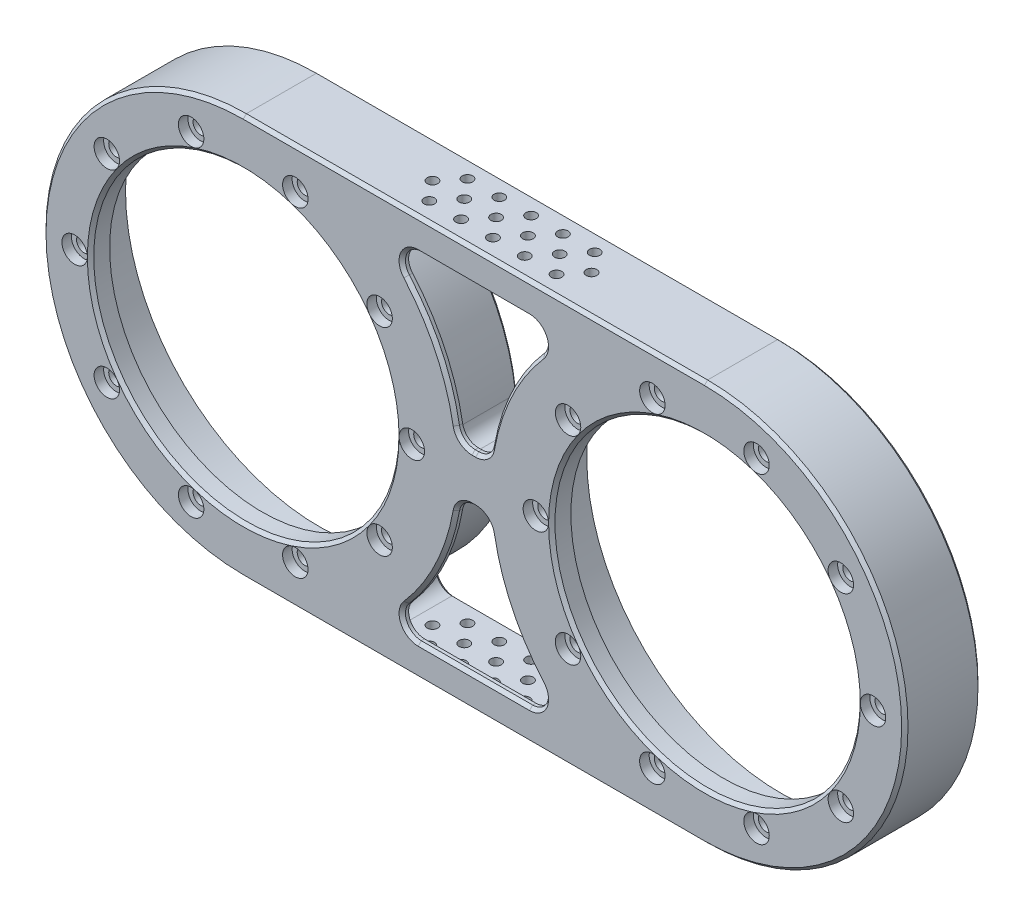
SolidWorks part; units mm, degrees
material "7075-T6 (SN)"
ref_plane "前视基准面" through (0, 0, 0) normal (0, 0, 1) x (1, 0, 0)
ref_plane "上视基准面" through (0, 0, 0) normal (0, 1, 0) x (1, 0, 0)
ref_plane "右视基准面" through (0, 0, 0) normal (1, 0, 0) x (0, 0, -1)
sketch "草图1" plane through (0, 0, 0) normal (0, 0, 1) x (1, 0, 0)
  line L0 (0, 63) -> (145, 63)
  line L1 (0, -63) -> (145, -63)
  arc A0 (0, 63) -> (0, -63) centre (0, 0) ccw
  arc A1 (145, -63) -> (145, 63) centre (145, 0) ccw
  circle A2 centre (0, 0) radius 60
  circle A3 centre (145, 0) radius 60
extrude "凸台-拉伸1" add sketch "草图1" against normal blind 3
sketch "草图2" plane through (0, 0, 0) normal (0, 0, 1) x (1, 0, 0)
  line L2 (0, -63) -> (145, -63)
  line L3 (145, 63) -> (0, 63)
  line L4 (0, -63) -> (145, -63)
  line L5 (145, 63) -> (0, 63)
  circle A0 centre (0, 0) radius 53 construction
  circle A1 centre (145, 0) radius 53 construction
  circle A2 centre (0, 0) radius 48
  circle A3 centre (145, 0) radius 48
  arc A6 (0, 63) -> (0, -63) centre (0, 0) ccw
  arc A7 (145, -63) -> (145, 63) centre (145, 0) ccw
  arc A8 (0, 63) -> (0, -63) centre (0, 0) ccw
  arc A9 (145, -63) -> (145, 63) centre (145, 0) ccw
  dimension "D1" = 5
  dimension "D2" = 5
  dimension "D3" = 0
extrude "凸台-拉伸2" add sketch "草图2" along normal blind 6
sketch "草图3" plane through (0, 0, -3) normal (0, 0, -1) x (-1, 0, 0)
  line L2 (0, 63) -> (-145, 63)
  line L3 (-145, -63) -> (0, -63)
  line L4 (0, 63) -> (-145, 63)
  line L5 (-145, -63) -> (0, -63)
  circle A0 centre (-145, 0) radius 61
  circle A1 centre (0, 0) radius 61
  arc A4 (0, -63) -> (0, 63) centre (0, 0) ccw
  arc A5 (-145, 63) -> (-145, -63) centre (-145, 0) ccw
  arc A6 (0, -63) -> (0, 63) centre (0, 0) ccw
  arc A7 (-145, 63) -> (-145, -63) centre (-145, 0) ccw
  dimension "D1" = 0
extrude "凸台-拉伸3" add sketch "草图3" along normal blind 15
sketch "草图4" plane through (0, 0, -18) normal (0, 0, -1) x (-1, 0, 0)
  line L0 (-84, 0) -> (-61, 0) construction
  line L1 (0, 58) -> (-145, 58)
  line L2 (0, 63) -> (-145, 63)
  line L3 (-145, -63) -> (0, -63)
  line L4 (0, 63) -> (-145, 63)
  line L5 (-145, -63) -> (0, -63)
  line L6 (-145, -58) -> (0, -58)
  line L7 (-84, -2.5) -> (-61, -2.5)
  line L8 (-84, 2.5) -> (-61, 2.5)
  circle A0 centre (0, 0) radius 61 construction
  circle A1 centre (-145, 0) radius 61 construction
  circle A2 centre (0, 0) radius 61
  circle A3 centre (-145, 0) radius 61
  circle A5 centre (-145, 0) radius 63
  arc A6 (0, -63) -> (0, 63) centre (0, 0) ccw
  arc A7 (-145, 63) -> (-145, -63) centre (-145, 0) ccw
  arc A8 (0, -63) -> (0, 63) centre (0, 0) ccw
  arc A9 (-145, 63) -> (-145, -63) centre (-145, 0) ccw
  circle A10 centre (0, 0) radius 63
  dimension "D2" = 5
  dimension "D1" = 0
  dimension "D3" = 5
  dimension "D4" = 2.5
  dimension "D5" = 2.5
extrude "切除-拉伸1" cut sketch "草图4" against normal blind 22
sketch "草图7" plane through (0, 0, 4) normal (0, 0, -1) x (-1, 0, 0)
  line L6 (-42.6028, 53) -> (-102.3972, 53)
  line L7 (-77.4149, 7.5) -> (-67.5851, 7.5)
  line L8 (-42.6028, 53) -> (-102.3972, 53)
  line L9 (-77.4149, 7.5) -> (-67.5851, 7.5)
  line L12 (-67.5851, -7.5) -> (-77.4149, -7.5)
  line L13 (-102.3972, -53) -> (-42.6028, -53)
  line L14 (-67.5851, -7.5) -> (-77.4149, -7.5)
  line L15 (-102.3972, -53) -> (-42.6028, -53)
  arc A6 (-42.6028, 53) -> (-67.5851, 7.5) centre (0, 0) ccw
  arc A7 (-77.4149, 7.5) -> (-102.3972, 53) centre (-145, 0) ccw
  arc A8 (-42.6028, 53) -> (-67.5851, 7.5) centre (0, 0) ccw
  arc A9 (-77.4149, 7.5) -> (-102.3972, 53) centre (-145, 0) ccw
  arc A12 (-67.5851, -7.5) -> (-42.6028, -53) centre (0, 0) ccw
  arc A13 (-102.3972, -53) -> (-77.4149, -7.5) centre (-145, 0) ccw
  arc A14 (-67.5851, -7.5) -> (-42.6028, -53) centre (0, 0) ccw
  arc A15 (-102.3972, -53) -> (-77.4149, -7.5) centre (-145, 0) ccw
  dimension "D1" = 5
  dimension "D2" = 5
extrude "切除-拉伸2" cut sketch "草图7" against normal blind 20
fillet "圆角2" radius 5 16 edges at (67.5851, 7.5, 5) (77.4149, 7.5, 5) (42.6028, -53, 5) (102.3972, -53, 5) (77.4149, -7.5, 5) (67.5851, -7.5, 5) (42.6028, 53, 5) (102.3972, 53, 5) (82.0496, 2.5, -7) (62.9504, 2.5, -7) (24.5967, 58, -7) (82.0496, -2.5, -7) (120.4033, -58, -7) (24.5967, -58, -7) (62.9504, -2.5, -7) (120.4033, 58, -7)
chamfer "倒角2" distance 1 angle 45 44 edges at (193, 0, 6) (72.5, 63, 6) (208, 0, 6) (72.5, -63, 6) (-63, 0, 6) (48, 0, 6) (68.7032, 8.6737, 6) (72.5, 7.5, 6) (76.2968, 8.6737, 6) (83.6169, 29.2595, 6) (94.5518, 50.069, 6) (72.5, 53, 6) (50.4482, 50.069, 6) (61.3831, 29.2595, 6) (50.4482, -50.069, 6) (72.5, -53, 6) (94.5518, -50.069, 6) (83.6169, -29.2595, 6) (76.2968, -8.6737, 6) (72.5, -7.5, 6) (68.7032, -8.6737, 6) (61.3831, -29.2595, 6) (60, 0, -3) (205, 0, -3) (89.7765, -30.3211, -18) (80.7497, -3.7746, -18) (107.1134, -54.6605, -18) (72.5, -2.5, -18) (72.5, -58, -18) (64.2503, -3.7746, -18) (37.8866, -54.6605, -18) (55.2235, -30.3211, -18) (72.5, -63, -18) (-63, 0, -18) (208, 0, -18) (72.5, 63, -18) (72.5, 2.5, -18) (64.2503, 3.7746, -18) (80.7497, 3.7746, -18) (55.2235, 30.3211, -18) (89.7765, 30.3211, -18) (37.8866, 54.6605, -18) (107.1134, 54.6605, -18) (72.5, 58, -18)
sketch "草图8" plane through (0, 0, 6) normal (0, 0, 1) x (1, 0, 0)
  circle A0 centre (145, 0) radius 53 construction
  circle A1 centre (0, 0) radius 53 construction
  point P6 (198, 0)
  point P7 (53, 0)
hole_wizard "打孔尺寸(%根据)内六角圆柱头螺钉的类型1" positions "草图9" profile "草图10" counterbore size "M4" standard "GB"
sketch "草图9" plane through (0, 0, 6) normal (0, 0, 1) x (1, 0, 0)
  point P0 (198, 0)
sketch "草图10" plane through (198, 0, 6) normal (1, 0, 0) x (0, -1, 0)
  line L0 (0, 0) -> (0, 11.5421)
  line L1 (0, 11.5421) -> (2.4, 10.1)
  line L2 (2.4, 10.1) -> (2.4, 3)
  line L3 (2.4, 3) -> (4, 3)
  line L4 (4, 3) -> (4, 0)
  line L5 (4, 0) -> (0, 0)
  line L10 (0, 11.5421) -> (-2.4, 10.1) construction
  line L11 (0, -6.35) -> (0, 107.95) construction
  dimension "孔直径" = 4.8
  dimension "孔深度" = 10.1
  dimension "柱形沉头孔直径" = 8
  dimension "柱形沉头孔深度" = 3
  dimension "导头角度" = 118
hole_wizard "打孔尺寸(%根据)内六角圆柱头螺钉的类型2" positions "草图11" profile "草图12" counterbore size "M4" standard "GB"
sketch "草图11" plane through (0, 0, 6) normal (0, 0, 1) x (1, 0, 0)
  point P0 (53, 0)
sketch "草图12" plane through (53, 0, 6) normal (1, 0, 0) x (0, -1, 0)
  line L0 (0, 0) -> (0, 11.5421)
  line L1 (0, 11.5421) -> (2.4, 10.1)
  line L2 (2.4, 10.1) -> (2.4, 3)
  line L3 (2.4, 3) -> (4, 3)
  line L4 (4, 3) -> (4, 0)
  line L5 (4, 0) -> (0, 0)
  line L10 (0, 11.5421) -> (-2.4, 10.1) construction
  line L11 (0, -6.35) -> (0, 107.95) construction
  dimension "孔直径" = 4.8
  dimension "孔深度" = 10.1
  dimension "柱形沉头孔直径" = 8
  dimension "柱形沉头孔深度" = 3
  dimension "导头角度" = 118
pattern_circular "阵列(圆周)1" count 10 every 36 about axis through (145, 0, 0) along (0, 0, 1) of "打孔尺寸(%根据)内六角圆柱头螺钉的类型1"
pattern_circular "阵列(圆周)2" count 10 every 36 about axis through (0, 0, 0) along (0, 0, 1) of "打孔尺寸(%根据)内六角圆柱头螺钉的类型2"
sketch "草图13" plane through (0, 63, 0) normal (0, 1, 0) x (1, 0, 0)
  line L0 (72.5, 18) -> (72.5, 12) construction
  line L1 (0, 18) -> (145, 18) construction
  line L2 (72.5, 12) -> (72.5, 6) construction
  line L4 (72.5, 6) -> (72.5, 0) construction
  line L5 (62.5, 12) -> (82.5, 12) construction
  line L6 (67.5, 6) -> (77.5, 6) construction
  line L7 (62.5, 0) -> (82.5, 0) construction
  line L8 (57.5, 6) -> (87.5, 6) construction
  line L9 (52.5, 12) -> (92.5, 12) construction
  line L10 (52.5, 0) -> (92.5, 0) construction
  line L11 (47.5, 6) -> (97.5, 6) construction
  point P7 (72.5, 12)
  point P12 (72.5, 6)
  point P17 (72.5, 0)
  point P20 (72.5, 6)
  point P23 (72.5, 12)
  point P25 (72.5, 0)
  point P30 (72.5, 6)
hole_wizard "M4 螺纹孔1" positions "草图17" profile "草图18" tap size "M4" standard "GB"
sketch "草图17" plane through (0, 63, 0) normal (0, 1, 0) x (1, 0, 0)
  point P5 (72.5, 12)
  point P8 (72.5, 0)
  point P11 (77.5, 6)
  point P14 (67.5, 6)
  point P17 (62.5, 12)
  point P20 (57.5, 6)
  point P23 (62.5, 0)
  point P26 (52.5, 0)
  point P29 (47.5, 6)
  point P32 (52.5, 12)
  point P35 (82.5, 12)
  point P38 (87.5, 6)
  point P41 (82.5, 0)
  point P44 (92.5, 0)
  point P47 (97.5, 6)
  point P50 (92.5, 12)
sketch "草图18" plane through (72.5, 63, -12) normal (1, 0, 0) x (0, 0, 1)
  line L0 (0, 0) -> (0, 11.0914)
  line L1 (0, 11.0914) -> (1.65, 10.1)
  line L2 (1.65, 10.1) -> (1.65, 0)
  line L5 (1.65, 0) -> (0, 0)
  line L10 (0, 11.0914) -> (-1.65, 10.1) construction
  line L11 (0, -6.35) -> (0, 107.95) construction
  dimension "螺纹孔钻头直径" = 3.3
  dimension "螺纹孔钻头深度" = 10.1
  dimension "导头角度" = 118
cosmetic thread "孔螺蚊线1" parameters "D1"=8, "D2"=4
cosmetic thread "孔螺蚊线2" parameters "D1"=8, "D2"=4
cosmetic thread "孔螺蚊线3" parameters "D1"=8, "D2"=4
cosmetic thread "孔螺蚊线4" parameters "D1"=8, "D2"=4
cosmetic thread "孔螺蚊线5" parameters "D1"=8, "D2"=4
cosmetic thread "孔螺蚊线6" parameters "D1"=8, "D2"=4
cosmetic thread "孔螺蚊线7" parameters "D1"=8, "D2"=4
cosmetic thread "孔螺蚊线8" parameters "D1"=8, "D2"=4
cosmetic thread "孔螺蚊线9" parameters "D1"=8, "D2"=4
cosmetic thread "孔螺蚊线10" parameters "D1"=8, "D2"=4
cosmetic thread "孔螺蚊线11" parameters "D1"=8, "D2"=4
cosmetic thread "孔螺蚊线12" parameters "D1"=8, "D2"=4
cosmetic thread "孔螺蚊线13" parameters "D1"=8, "D2"=4
cosmetic thread "孔螺蚊线14" parameters "D1"=8, "D2"=4
cosmetic thread "孔螺蚊线15" parameters "D1"=8, "D2"=4
cosmetic thread "孔螺蚊线16" parameters "D1"=8, "D2"=4
ref_plane "基准面1" through (0, 0, 0) normal (0, 1, 0) x (1, 0, 0)
mirror "镜向1" about plane through (0, 0, 0) normal (0, 1, 0) of "M4 螺纹孔1"
cosmetic thread "孔螺蚊线17" parameters "D1"=8, "D2"=4
cosmetic thread "孔螺蚊线18" parameters "D1"=8, "D2"=4
cosmetic thread "孔螺蚊线19" parameters "D1"=8, "D2"=4
cosmetic thread "孔螺蚊线20" parameters "D1"=8, "D2"=4
cosmetic thread "孔螺蚊线21" parameters "D1"=8, "D2"=4
cosmetic thread "孔螺蚊线22" parameters "D1"=8, "D2"=4
cosmetic thread "孔螺蚊线23" parameters "D1"=8, "D2"=4
cosmetic thread "孔螺蚊线24" parameters "D1"=8, "D2"=4
cosmetic thread "孔螺蚊线25" parameters "D1"=8, "D2"=4
cosmetic thread "孔螺蚊线26" parameters "D1"=8, "D2"=4
cosmetic thread "孔螺蚊线27" parameters "D1"=8, "D2"=4
cosmetic thread "孔螺蚊线28" parameters "D1"=8, "D2"=4
cosmetic thread "孔螺蚊线29" parameters "D1"=8, "D2"=4
cosmetic thread "孔螺蚊线30" parameters "D1"=8, "D2"=4
cosmetic thread "孔螺蚊线31" parameters "D1"=8, "D2"=4
cosmetic thread "孔螺蚊线32" parameters "D1"=8, "D2"=4
